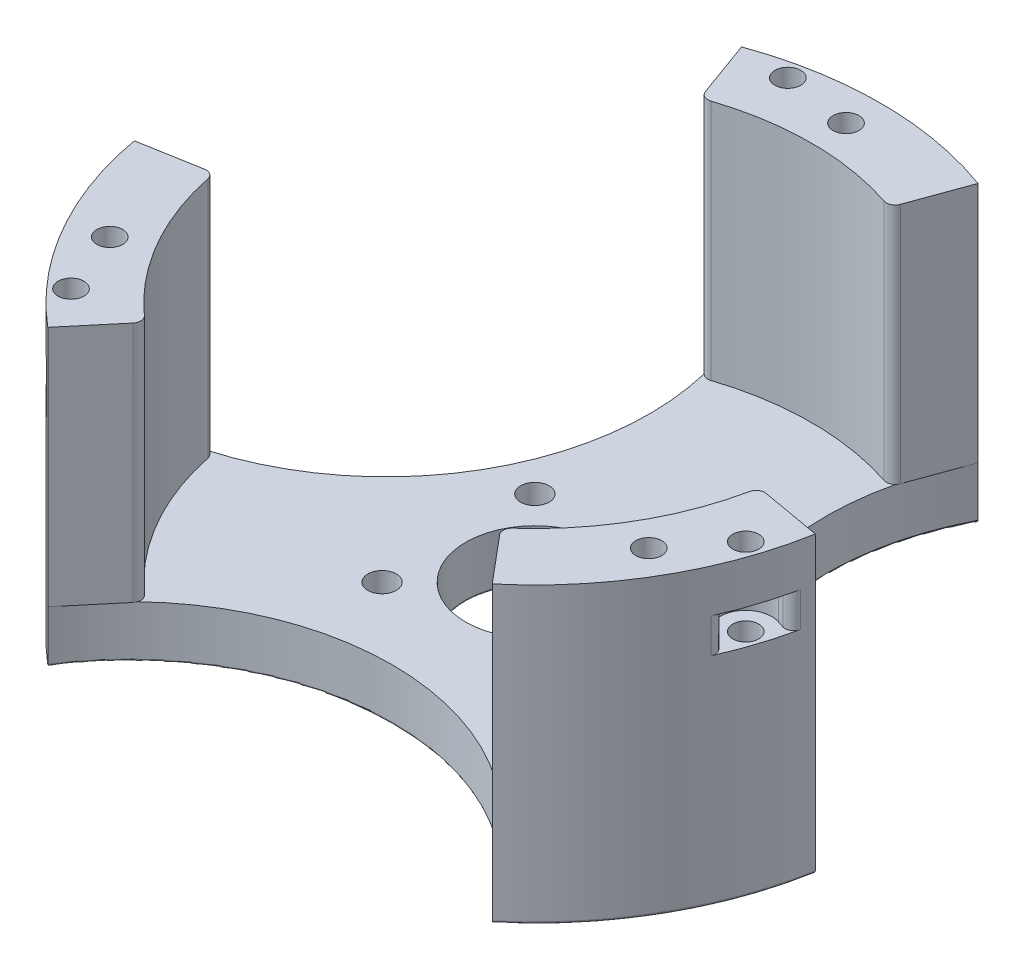
SolidWorks part; units mm, degrees
ref_plane "Front Plane" through (0, 0, 0) normal (0, 0, 1) x (1, 0, 0)
ref_plane "Top Plane" through (0, 0, 0) normal (0, 1, 0) x (1, 0, 0)
ref_plane "Right Plane" through (0, 0, 0) normal (1, 0, 0) x (0, 0, -1)
sketch "Sketch1" plane through (0, 0, 0) normal (0, 1, 0) x (1, 0, 0)
  line L1 (-8.8388, -8.8388) -> (8.8388, -8.8388) construction
  line L2 (-8.8388, -8.8388) -> (-8.8388, 8.8388) construction
  line L3 (-8.8388, 8.8388) -> (8.8388, 8.8388) construction
  line L4 (8.8388, -8.8388) -> (8.8388, 8.8388) construction
  line L5 (-8.8388, -8.8388) -> (8.8388, 8.8388) construction
  line L6 (-8.8388, 8.8388) -> (8.8388, -8.8388) construction
  circle A0 centre (0, 0) radius 40
  circle A1 centre (-8.8388, 8.8388) radius 1.65
  circle A2 centre (8.8388, 8.8388) radius 1.65
  circle A3 centre (8.8388, -8.8388) radius 1.65
  circle A4 centre (-8.8388, -8.8388) radius 1.65
  dimension "D1" = 80
  dimension "D4" = 3.3
  dimension "D2" = 12.5
extrude "Boss-Extrude1" add sketch "Sketch1" along normal blind 6
sketch "Sketch2" plane through (0, 6, 0) normal (0, 1, 0) x (1, 0, 0)
  line L0 (-13.6808, 37.5877) -> (0, 0) construction
  line L1 (0, 0) -> (13.6808, 37.5877) construction
  line L2 (0, -1000) -> (0, 49000) construction
  line L3 (-13.6808, 37.5877) -> (-10.9446, 30.0702)
  line L4 (10.9446, 30.0702) -> (13.6808, 37.5877)
  arc A0 (13.6808, 37.5877) -> (-13.6808, 37.5877) centre (0, 0) ccw
  circle A1 centre (0, 0) radius 40 construction
  arc A2 (10.9446, 30.0702) -> (-10.9446, 30.0702) centre (0, 0) ccw
  circle A3 centre (0, 36) radius 1.5
  dimension "D1" = 8
  dimension "D5" = 3
  dimension "D2" = 20
  dimension "D3" = 20
  dimension "D4" = 36
extrude "Boss-Extrude2" add sketch "Sketch2" along normal blind 28
sketch "Sketch16" plane through (0, 34, 0) normal (0, 1, 0) x (1, 0, 0)
  circle A0 centre (0, 36) radius 1.5
  circle A1 centre (0, 36) radius 1.5 construction
extrude "Cut-Extrude9" cut sketch "Sketch16" against normal through all
pattern_circular "CirPattern1" count 3 over 360 about axis through (0, 0, 0) along (0, 1, 0) of "Boss-Extrude2", "Cut-Extrude9"
sketch "Sketch3" plane through (0, 6, 0) normal (0, 1, 0) x (1, 0, 0)
  circle A0 centre (0, 0) radius 8
  dimension "D1" = 16
extrude "Cut-Extrude1" cut sketch "Sketch3" against normal blind 10
sketch "Sketch4" plane through (0, 0, 0) normal (0, -1, 0) x (1, 0, 0)
  circle A0 centre (8.8388, 8.8388) radius 3.5
  circle A1 centre (8.8388, -8.8388) radius 3.5
  circle A2 centre (-8.8388, -8.8388) radius 3.5
  circle A3 centre (-8.8388, 8.8388) radius 3.5
  dimension "D1" = 7
extrude "Cut-Extrude2" cut sketch "Sketch4" against normal blind 3
sketch "Sketch5" plane through (0, 6, 0) normal (0, 1, 0) x (1, 0, 0)
  circle A1 centre (40.6986, 23.4973) radius 30.4713
extrude "Cut-Extrude3" cut sketch "Sketch5" against normal through all
pattern_circular "CirPattern2" count 3 over 360 about axis through (0, 0, 0) along (0, 1, 0) of "Cut-Extrude3"
fillet "Fillet1" radius 0.25 14 edges at (-8.8388, 0, -12.3388) (8.8388, 0, -12.3388) (8.8388, 0, 5.3388) (0, 0, -40) (14.3097, 0, -8.2617) (-34.641, 0, 20) (34.641, 0, 20) (-14.3097, 0, -8.2617) (0, 0, 16.5234) (0, 0, -34.5) (-29.8779, 0, 17.25) (29.8779, 0, 17.25) (0, 0, 8) (-8.8388, 0, 5.3388)
fillet "Fillet2" radius 1 6 edges at (31.5138, 20, 5.5567) (10.9446, 20, -30.0702) (-10.9446, 20, -30.0702) (20.5692, 20, 24.5134) (-31.5138, 20, 5.5567) (-20.5692, 20, 24.5134)
sketch "Sketch6" plane through (0, 34, 0) normal (0, 1, 0) x (1, 0, 0)
  line L0 (0, 36) -> (0, 0) construction
  line L1 (0, 0) -> (-31.1769, -18) construction
  line L2 (0, 0) -> (31.1769, -18) construction
  circle A0 centre (0, 0) radius 6
  circle A1 centre (15.5885, -9) radius 12
  circle A2 centre (0, 18) radius 12
  circle A3 centre (-15.5885, -9) radius 12
  point P7 (15.5885, -9)
  point P9 (0, 18)
  point P10 (-15.5885, -9)
  dimension "D1" = 12
  dimension "D2" = 24
sketch "Sketch7" plane through (0, 34, 0) normal (0, 1, 0) x (1, 0, 0)
  circle A0 centre (0, 0) radius 18
  circle A1 centre (0, 0) radius 13
  dimension "D1" = 26
  dimension "D2" = 5
ref_plane "Plane1" through (0, 29, 0) normal (0, 1, 0) x (1, 0, 0)
sketch "Sketch9" plane through (0, 29, 0) normal (0, 1, 0) x (1, 0, 0)
  line L0 (-7.9006, 37.1696) -> (0, 0) construction
  line L1 (-15.3328, 38.1457) -> (-7.5822, 39.7932) construction
  line L2 (0, 36) -> (0, 0) construction
  circle A0 centre (-7.9006, 37.1696) radius 2.5 construction
  circle A1 centre (-7.9006, 37.1696) radius 1.5
  arc A4 (13.6808, 37.5877) -> (-13.6808, 37.5877) centre (0, 0) ccw construction
  dimension "D1" = 5
  dimension "D2" = 3
  dimension "D3" = 40.5
  dimension "D4" = 12
extrude "Cut-Extrude4" cut sketch "Sketch9" against normal through all and the other way through all
sketch "Sketch10" plane through (0, 29, 0) normal (0, 1, 0) x (1, 0, 0)
  line L0 (-11.5628, 39.9694) -> (-10.8351, 36.5459)
  line L1 (-5.6939, 41.2169) -> (-4.9662, 37.7933)
  line L2 (-7.9006, 37.1696) -> (0, 0) construction
  line L3 (-11.5628, 39.9694) -> (-5.6939, 41.2169)
  line L4 (-15.3328, 38.1457) -> (-7.5822, 39.7932) construction
  arc A0 (-10.8351, 36.5459) -> (-4.9662, 37.7933) centre (-7.9006, 37.1696) ccw
  dimension "D1" = 6
  dimension "D2" = 1
extrude "Cut-Extrude5" cut sketch "Sketch10" against normal blind 4
fillet "Fillet3" radius 1 2 edges at (-11.2275, 27, -38.392) (-5.3586, 27, -39.6394)
pattern_circular "CirPattern3" count 3 over 360 about axis through (0, 0, 0) along (0, 1, 0) of "Cut-Extrude4", "Cut-Extrude5", "Fillet3"
